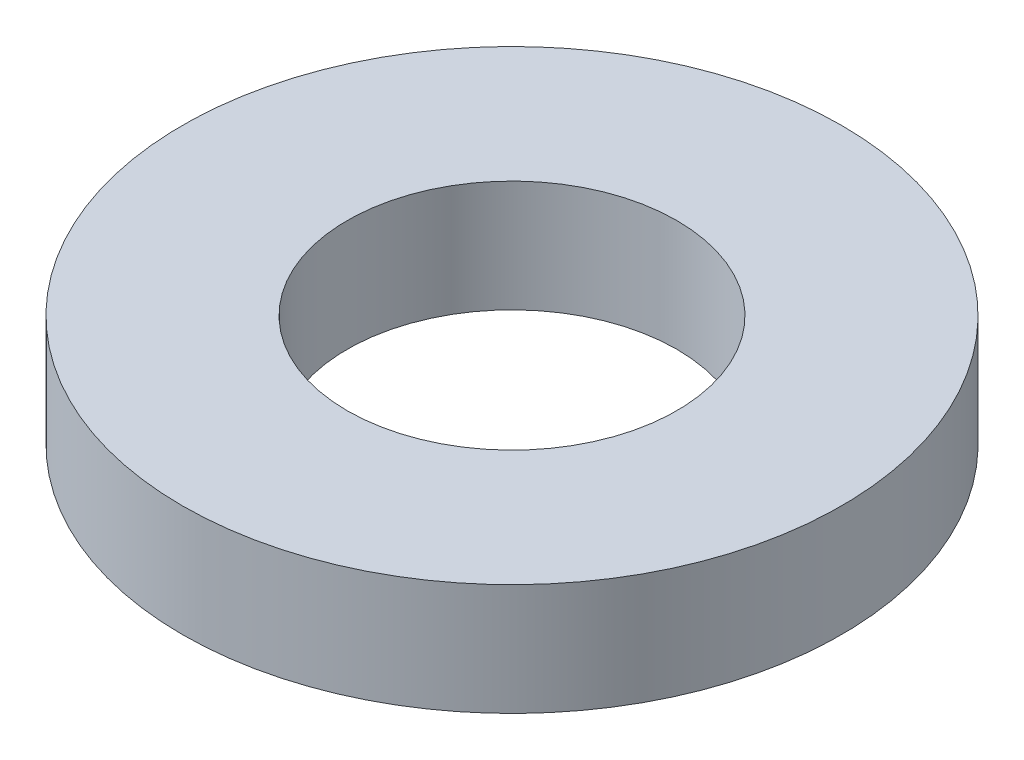
SolidWorks part; units mm, degrees
ref_plane "Front Plane" through (0, 0, 0) normal (0, 0, 1) x (1, 0, 0)
ref_plane "Top Plane" through (0, 0, 0) normal (0, 1, 0) x (1, 0, 0)
ref_plane "Right Plane" through (0, 0, 0) normal (1, 0, 0) x (0, 0, -1)
sketch "Sketch1" plane through (0, 0, 0) normal (0, 1, 0) x (1, 0, 0)
  circle A0 centre (0, 0) radius 65
  dimension "FLANGE_OD" = 130
extrude "Boss-Extrude1" add sketch "Sketch1" along normal blind 22
sketch "Sketch2" plane through (0, 0, 0) normal (0, 1, 0) x (1, 0, 0)
  circle A0 centre (0, 0) radius 32.5
  dimension "BORE_D" = 65
extrude "Cut-Extrude1" cut sketch "Sketch2" along normal through all
sketch "Sketch3" plane through (0, 22, 0) normal (0, 1, 0) x (1, 0, 0)
  circle A0 centre (0, 0) radius 21.1014 construction
  circle A1 centre (-21.1014, 0) radius 3.4477
  dimension "BOLT_D" = 6.8953
  dimension "BOLT_PCD" = 42.2028
extrude "Cut-Extrude2" cut sketch "Sketch3" against normal blind 15.253 rebuild error yes
pattern_circular "CirPattern1" count 6 over 360 rebuild error yes
